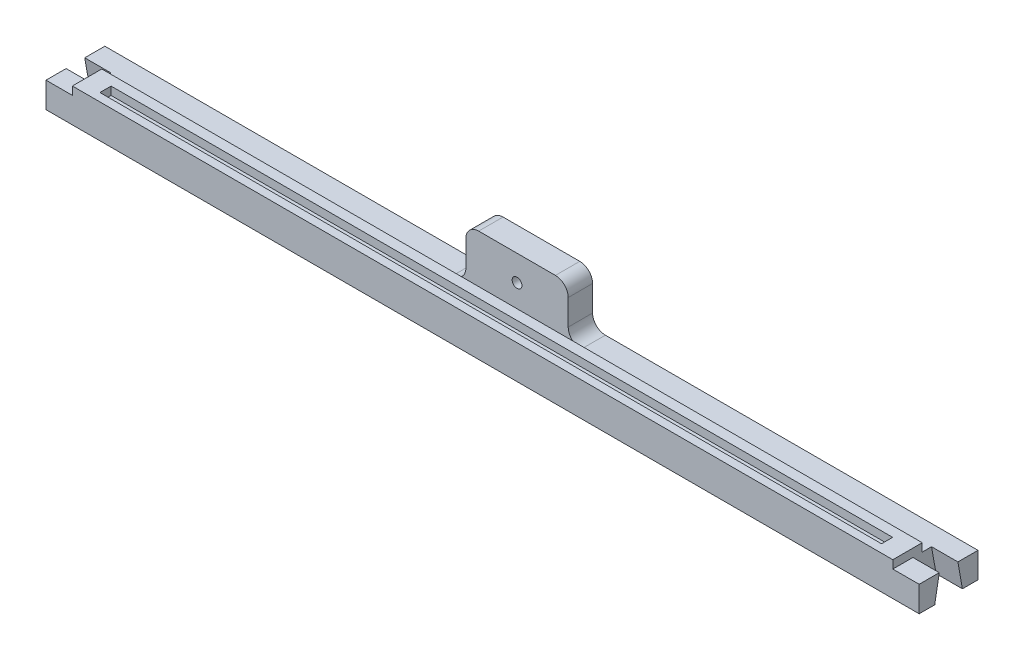
SolidWorks part; units mm, degrees
ref_plane "Front Plane" through (0, 0, 0) normal (0, 0, 1) x (1, 0, 0)
ref_plane "Top Plane" through (0, 0, 0) normal (0, 1, 0) x (1, 0, 0)
ref_plane "Right Plane" through (0, 0, 0) normal (1, 0, 0) x (0, 0, -1)
sketch "Sketch1" plane through (0, 0, 0) normal (0, 1, 0) x (1, 0, 0)
  line L0 (-320.75, 23) -> (-320.75, 7.291)
  line L1 (-341.35, 23) -> (341.35, 23)
  line L2 (-341.35, 23) -> (-341.35, -23)
  line L3 (-341.35, -23) -> (341.35, -23)
  line L4 (341.35, 23) -> (341.35, -23)
  line L5 (-341.35, 23) -> (341.35, -23) construction
  line L6 (-341.35, -23) -> (341.35, 23) construction
  line L7 (320.75, 23) -> (320.75, -23)
  line L8 (-320.75, -7.291) -> (-320.75, -23)
  line L9 (-320.75, 7.291) -> (-320.75, -7.291)
  line L10 (-320.75, 7.291) -> (-341.35, 7.291)
  line L11 (-320.75, -7.291) -> (-341.35, -7.291)
  line L12 (0, 23) -> (0, -23) construction
  line L13 (320.75, -7.291) -> (341.35, -7.291)
  line L14 (320.75, 7.291) -> (341.35, 7.291)
  point P0 (0, 0)
  dimension "D1" = 20.6
  dimension "D2" = 20.6
  dimension "D3" = 46
  dimension "D4" = 641.5
  dimension "D5" = 15.709
  dimension "D6" = 14.582
extrude "Boss-Extrude1" add sketch "Sketch1" along normal blind 20 contours L2 L3 L0 L1 | L7 L1 L0 L3 | L8 L11 L2 L3 | L13 L7 L3 L4 | L7 L14 L4 L1
sketch "Sketch2" plane through (0, 20, 0) normal (0, 1, 0) x (1, 0, 0)
  line L0 (-305.55, 0) -> (305.55, 0)
  line L1 (-341.35, -23) -> (341.35, -23)
  line L2 (-341.35, -23) -> (-341.35, -7.9188)
  line L3 (-341.35, -7.9188) -> (341.35, -7.9188)
  line L4 (341.35, -23) -> (341.35, -7.9188)
  line L5 (341.35, 23) -> (341.35, 7.291) construction
  line L6 (-341.35, -23) -> (341.35, -23)
  line L7 (-341.35, -23) -> (-341.35, -16.65)
  line L8 (-341.35, -16.65) -> (341.35, -16.65)
  line L9 (341.35, -23) -> (341.35, -16.65)
  line L10 (-341.35, -7.9188) -> (341.35, -7.9188)
  line L11 (-341.35, -7.9188) -> (-341.35, -1.5688)
  line L12 (-341.35, -1.5688) -> (341.35, -1.5688)
  line L13 (341.35, -7.9188) -> (341.35, -1.5688)
  line L14 (305.55, 23) -> (305.55, -23)
  line L15 (-341.35, 23) -> (341.35, 23) construction
  line L16 (-305.55, 23) -> (-305.55, -23)
  line L17 (0, 23) -> (0, -23) construction
  line L18 (-305.55, -23) -> (-320.75, -23)
  line L19 (-305.55, -23) -> (-305.55, 0)
  line L20 (-305.55, 0) -> (-320.75, 0)
  line L21 (-320.75, -23) -> (-320.75, 0)
  line L22 (305.55, 0) -> (320.75, 0)
  line L23 (320.75, -23) -> (320.75, 0)
  point P15 (0, 0)
  line M5 (-341.35, -23) -> (341.35, -23)
  line M6 (341.35, -23) -> (341.35, -7.291)
  dimension "D1" = 15.0812
  dimension "D2" = 6.35
  dimension "D3" = 21.4312
  dimension "D4" = 611.1
  dimension "D5" = 641.5
extrude "Boss-Extrude2" add sketch "Sketch2" along normal blind 6.35 contours L8 L2 M5 M6 | L12 L16 L0 L14 | L12 L17 L3 L14 | L8 L17 L14 M5 | L12 L23 L22 L14 | L10 L23 L12 L14 | L8 L23 L10 L14 | L6 L23 L8 L14 | L21 L12 L16 L20 | L21 L10 L16 L12 | L21 L8 L16 L10 | L21 L6 L16 L8 | L17 L12 L16 L10 | L0 L17 L12 L14
sketch "Sketch4" plane through (0, 20, 0) normal (0, 1, 0) x (1, 0, 0)
  line L0 (-341.35, 23) -> (341.35, 23) construction
  line L1 (-40, 3.95) -> (40, 3.95)
  line L2 (-40, 3.95) -> (-40, 42.05)
  line L3 (-40, 42.05) -> (40, 42.05)
  line L4 (40, 3.95) -> (40, 42.05)
  line L5 (-40, 3.95) -> (40, 42.05) construction
  line L6 (-40, 42.05) -> (40, 3.95) construction
  line L7 (-40, 23) -> (40, 23)
  point P0 (0, 23)
  line M11 (341.35, 23) -> (-341.35, 23)
  dimension "D1" = 80
  dimension "D2" = 38.1
extrude "Boss-Extrude3" add sketch "Sketch4" along normal blind 40 contours L1 L4 L2 M11
sketch "Sketch5" plane through (0, 0, -23) normal (0, 0, -1) x (-1, 0, 0)
  line L0 (-40, 60) -> (40, 20)
  line L1 (-40, 20) -> (40, 20)
  line L2 (-40, 20) -> (-40, 60)
  line L3 (-40, 60) -> (40, 60)
  line L4 (40, 20) -> (40, 60)
  line L5 (40, 60) -> (-40, 20)
  circle A0 centre (0, 40) radius 3.81
  dimension "D1" = 7.62
extrude "Cut-Extrude2" cut sketch "Sketch5" against normal blind 50.8 contours L5 A0 L0 | L0 A0 L5 | L5 A0 L0 | L0 A0 L5
chamfer "Chamfer1" distance 20 angle 10 4 edges at (331.05, 0, -7.291) (331.05, 0, 7.291) (-331.05, 0, 7.291) (-331.05, 0, -7.291)
fillet "Fillet1" radius 10 4 edges at (40, 60, -13.475) (-40, 60, -13.475) (-40, 20, -13.475) (40, 20, -13.475)
